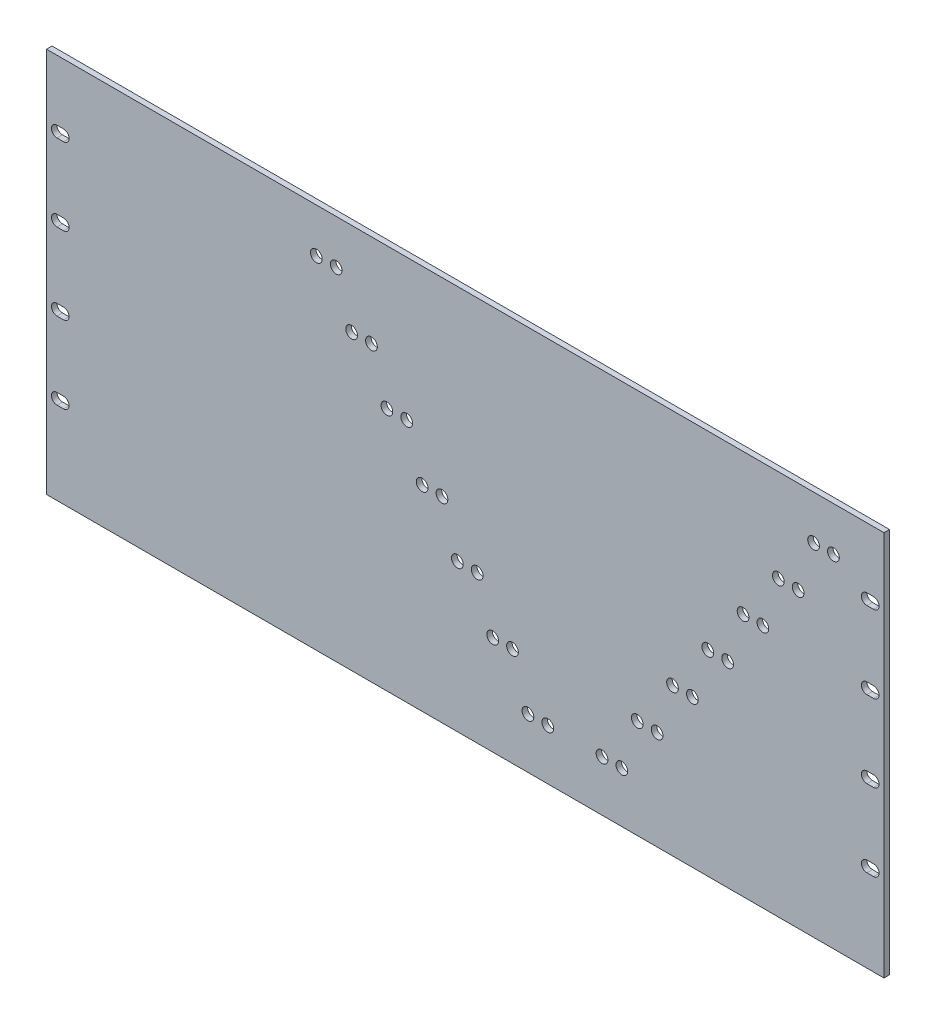
SolidWorks part; units mm, degrees
material "6061 Alloy"
ref_plane "Front Plane" through (0, 0, 0) normal (0, 0, 1) x (1, 0, 0)
ref_plane "Top Plane" through (0, 0, 0) normal (0, 1, 0) x (1, 0, 0)
ref_plane "Right Plane" through (0, 0, 0) normal (1, 0, 0) x (0, 0, -1)
sketch "Sketch1" plane through (0, 0, 0) normal (0, 0, 1) x (1, 0, 0)
  line L1 (0, 0) -> (482.6, 0)
  line L2 (0, 0) -> (0, 222.25)
  line L3 (0, 222.25) -> (482.6, 222.25)
  line L4 (482.6, 0) -> (482.6, 222.25)
  dimension "D1" = 482.6
  dimension "D2" = 222.25
extrude "Boss-Extrude1" add sketch "Sketch1" along normal blind 3.175
hole_wizard "1/4 Clearance Hole1" positions "Sketch2" profile "Sketch3" hole size "1/4" standard "ANSI Inch"
sketch "Sketch2" plane through (-396.9991, -1332.6219, 0) normal (0, 0, -1) x (-1, 0, 0)
  point P0 (-850.4679, 1529.4719)
  point P3 (-839.0379, 1529.4719)
  point P6 (-830.1479, 1501.5319)
  point P9 (-818.7179, 1501.5319)
  point P12 (-809.8279, 1473.5919)
  point P15 (-798.3979, 1473.5919)
  point P18 (-789.5079, 1445.6519)
  point P21 (-778.0779, 1445.6519)
  point P24 (-769.1879, 1417.7119)
  point P27 (-757.7579, 1417.7119)
  point P30 (-748.8679, 1389.7719)
  point P33 (-737.4379, 1389.7719)
  point P36 (-728.5479, 1361.8319)
  point P39 (-717.1179, 1361.8319)
  point P42 (-685.8441, 1361.8319)
  point P45 (-674.4141, 1361.8319)
  point P48 (-665.5241, 1389.7719)
  point P51 (-654.0941, 1389.7719)
  point P54 (-645.2041, 1417.7119)
  point P57 (-633.7741, 1417.7119)
  point P60 (-624.8841, 1445.6519)
  point P63 (-613.4541, 1445.6519)
  point P66 (-604.5641, 1473.5919)
  point P69 (-593.1341, 1473.5919)
  point P72 (-584.2441, 1501.5319)
  point P75 (-572.8141, 1501.5319)
  point P78 (-563.9241, 1529.4719)
  point P81 (-552.4941, 1529.4719)
sketch "Sketch3" plane through (453.4687, 196.85, 0) normal (1, 0, 0) x (0, 1, 0)
  line L0 (0, 0) -> (0, 21.0798)
  line L1 (0, 21.0798) -> (3.3782, 19.05)
  line L2 (3.3782, 19.05) -> (3.3782, 0)
  line L3 (3.3782, 0) -> (0, 0)
  line L4 (0, 21.0798) -> (-3.3782, 19.05) construction
  line L5 (0, -6.35) -> (0, 107.95) construction
  dimension "Hole Dia." = 6.7564
  dimension "Hole Depth" = 19.05
  dimension "Drill Angle" = 118
hole_wizard "Tap Drill Slot for #10-24 Tap1" positions "Sketch5" profile "Sketch4" size "#10-24" standard "ANSI Inch" slot yes
sketch "Sketch5" plane through (0, 0, 3.175) normal (0, 0, 1) x (1, 0, 0)
  line L0 (241.3, 222.25) -> (241.3, 0) construction
  line L1 (482.6, 222.25) -> (0, 222.25) construction
  line L2 (0, 0) -> (482.6, 0) construction
  line L4 (7.9248, 222.25) -> (7.9248, 0) construction
  line L5 (2.8448, 184.15) -> (13.0048, 184.15) construction
  point P13 (7.9248, 184.15)
  point P17 (7.9248, 139.7)
  point P19 (7.9248, 95.25)
  point P21 (7.9248, 50.8)
  point P22 (474.6752, 50.8)
  point P23 (474.6752, 95.25)
  point P24 (474.6752, 139.7)
  point P25 (474.6752, 184.15)
  dimension "D1" = 233.3752
  dimension "D2" = 10.16
  dimension "D3" = 38.1
  dimension "D4" = 44.45
  dimension "D5" = 44.45
  dimension "D6" = 44.45
sketch "Sketch4" plane through (7.9248, 184.15, 3.175) normal (1, 0, 0) x (0, -1, 0)
  line L0 (0, 0) -> (0, 5.2097)
  line L1 (0, 5.2097) -> (3.175, 3.302)
  line L2 (3.175, 3.302) -> (3.175, 0)
  line L5 (3.175, 0) -> (0, 0)
  line L10 (0, 5.2097) -> (-3.175, 3.302) construction
  line L11 (0, -6.35) -> (0, 107.95) construction
  dimension "Hole Dia." = 6.35
  dimension "Hole Depth" = 3.302
  dimension "Drill Angle" = 118
